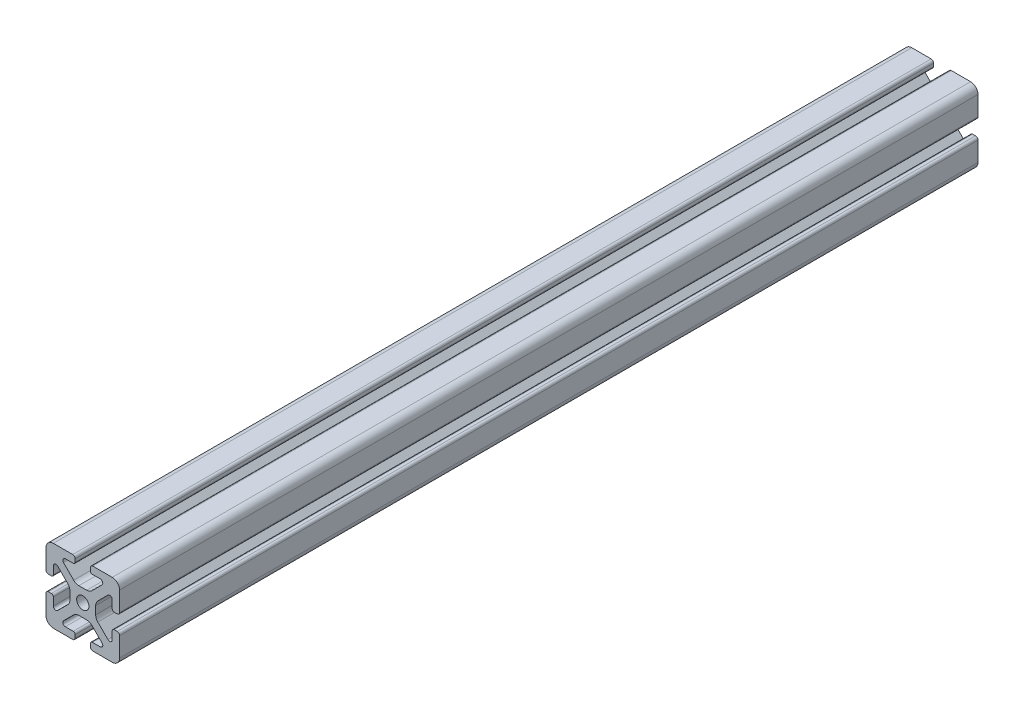
SolidWorks part; units mm, degrees
material "3003 Alloy"
ref_plane "Front Plane" through (0, 0, 0) normal (0, 0, 1) x (1, 0, 0)
ref_plane "Top Plane" through (0, 0, 0) normal (0, 1, 0) x (1, 0, 0)
ref_plane "Right Plane" through (0, 0, 0) normal (1, 0, 0) x (0, 0, -1)
sketch "Sketch1" plane through (0, 0, 0) normal (0, 0, 1) x (1, 0, 0)
  point P0 (5.1249, 1.9668)
  line B0 (1.6032, 5.25) -> (-1.6032, 5.25)
  arc B1 (-12, 15) -> (-15, 12) centre (-12, 12) ccw
  line B2 (-7.1276, 12) -> (-3.9, 12)
  line B3 (7.8506, 10.2547) -> (3.7245, 6.1287)
  line B4 (-10.2547, 7.8506) -> (-6.1287, 3.7245)
  line B5 (3.1, -12.8) -> (3.1, -14)
  arc B6 (3.9, -12) -> (3.1, -12.8) centre (3.9, -12.8) ccw
  line B7 (7.1276, -12) -> (3.9, -12)
  arc B8 (7.1276, -12) -> (7.8506, -10.2547) centre (7.1276, -10.9776) ccw
  line B9 (3.7245, -6.1287) -> (7.8506, -10.2547)
  arc B10 (3.7245, -6.1287) -> (1.6032, -5.25) centre (1.6032, -8.25) ccw
  line B11 (-1.6032, -5.25) -> (1.6032, -5.25)
  arc B12 (-1.6032, -5.25) -> (-3.7245, -6.1287) centre (-1.6032, -8.25) ccw
  line B13 (-7.8506, -10.2547) -> (-3.7245, -6.1287)
  arc B14 (-7.8506, -10.2547) -> (-7.1276, -12) centre (-7.1276, -10.9776) ccw
  line B15 (-3.9, -12) -> (-7.1276, -12)
  arc B16 (-3.1, -12.8) -> (-3.9, -12) centre (-3.9, -12.8) ccw
  line B17 (-3.1, -14) -> (-3.1, -12.8)
  arc B18 (-4.1, -15) -> (-3.1, -14) centre (-4.1, -14) ccw
  line B19 (-12, -15) -> (-4.1, -15)
  arc B20 (-15, -12) -> (-12, -15) centre (-12, -12) ccw
  line B21 (-15, -4.1) -> (-15, -12)
  arc B22 (-14, -3.1) -> (-15, -4.1) centre (-14, -4.1) ccw
  line B23 (-12.8, -3.1) -> (-14, -3.1)
  arc B24 (-12, -3.9) -> (-12.8, -3.1) centre (-12.8, -3.9) ccw
  line B25 (-12, -7.1276) -> (-12, -3.9)
  arc B26 (-12, -7.1276) -> (-10.2547, -7.8506) centre (-10.9776, -7.1276) ccw
  line B27 (-6.1287, -3.7245) -> (-10.2547, -7.8506)
  arc B28 (-6.1287, -3.7245) -> (-5.25, -1.6032) centre (-8.25, -1.6032) ccw
  line B29 (-5.25, 1.6032) -> (-5.25, -1.6032)
  arc B30 (-5.25, 1.6032) -> (-6.1287, 3.7245) centre (-8.25, 1.6032) ccw
  arc B31 (-10.2547, 7.8506) -> (-12, 7.1276) centre (-10.9776, 7.1276) ccw
  line B32 (-12, 3.9) -> (-12, 7.1276)
  arc B33 (-12.8, 3.1) -> (-12, 3.9) centre (-12.8, 3.9) ccw
  line B34 (-14, 3.1) -> (-12.8, 3.1)
  arc B35 (-15, 4.1) -> (-14, 3.1) centre (-14, 4.1) ccw
  line B36 (-15, 12) -> (-15, 4.1)
  line B37 (-4.1, 15) -> (-12, 15)
  arc B38 (-3.1, 14) -> (-4.1, 15) centre (-4.1, 14) ccw
  line B39 (-3.1, 12.8) -> (-3.1, 14)
  arc B40 (-3.9, 12) -> (-3.1, 12.8) centre (-3.9, 12.8) ccw
  arc B41 (-7.1276, 12) -> (-7.8506, 10.2547) centre (-7.1276, 10.9776) ccw
  line B42 (-3.7245, 6.1287) -> (-7.8506, 10.2547)
  arc B43 (-3.7245, 6.1287) -> (-1.6032, 5.25) centre (-1.6032, 8.25) ccw
  arc B44 (1.6032, 5.25) -> (3.7245, 6.1287) centre (1.6032, 8.25) ccw
  arc B45 (7.8506, 10.2547) -> (7.1276, 12) centre (7.1276, 10.9776) ccw
  line B46 (3.9, 12) -> (7.1276, 12)
  arc B47 (3.1, 12.8) -> (3.9, 12) centre (3.9, 12.8) ccw
  line B48 (3.1, 14) -> (3.1, 12.8)
  arc B49 (4.1, 15) -> (3.1, 14) centre (4.1, 14) ccw
  line B50 (12, 15) -> (4.1, 15)
  arc B51 (15, 12) -> (12, 15) centre (12, 12) ccw
  line B52 (15, 4.1) -> (15, 12)
  arc B53 (14, 3.1) -> (15, 4.1) centre (14, 4.1) ccw
  line B54 (12.8, 3.1) -> (14, 3.1)
  arc B55 (12, 3.9) -> (12.8, 3.1) centre (12.8, 3.9) ccw
  line B56 (12, 7.1276) -> (12, 3.9)
  arc B57 (12, 7.1276) -> (10.2547, 7.8506) centre (10.9776, 7.1276) ccw
  line B58 (6.1287, 3.7245) -> (10.2547, 7.8506)
  arc B59 (6.1287, 3.7245) -> (5.25, 1.6032) centre (8.25, 1.6032) ccw
  line B60 (5.25, -1.6032) -> (5.25, 1.6032)
  arc B61 (5.25, -1.6032) -> (6.1287, -3.7245) centre (8.25, -1.6032) ccw
  line B62 (10.2547, -7.8506) -> (6.1287, -3.7245)
  arc B63 (10.2547, -7.8506) -> (12, -7.1276) centre (10.9776, -7.1276) ccw
  line B64 (12, -3.9) -> (12, -7.1276)
  arc B65 (12.8, -3.1) -> (12, -3.9) centre (12.8, -3.9) ccw
  line B66 (14, -3.1) -> (12.8, -3.1)
  arc B67 (15, -4.1) -> (14, -3.1) centre (14, -4.1) ccw
  line B68 (15, -12) -> (15, -4.1)
  arc B69 (12, -15) -> (15, -12) centre (12, -12) ccw
  line B70 (4.1, -15) -> (12, -15)
  arc B71 (3.1, -14) -> (4.1, -15) centre (4.1, -14) ccw
  circle B72 centre (0, 0) radius 2.5
sketch_block_instance "IR 30X30 IR41901-2"
sketch_block "IR 30X30 IR41901"
extrude "Boss-Extrude1" add sketch "Sketch1" along normal blind 350
